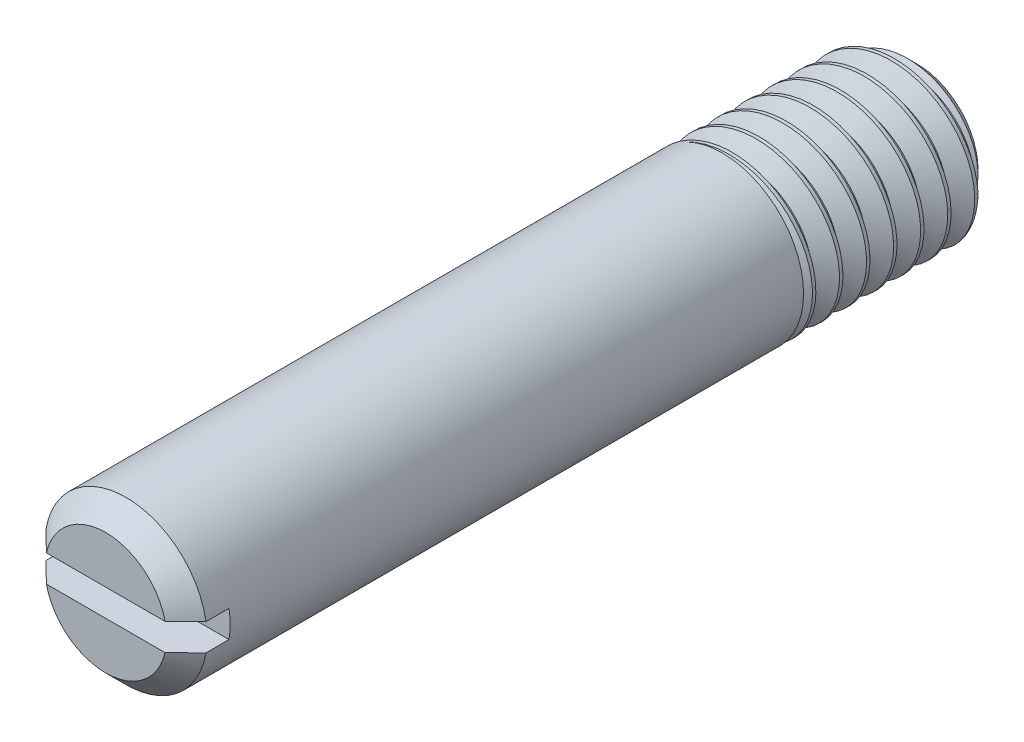
SolidWorks part; units mm, degrees
ref_plane "Front Plane" through (0, 0, 0) normal (0, 0, 1) x (1, 0, 0)
ref_plane "Top Plane" through (0, 0, 0) normal (0, 1, 0) x (1, 0, 0)
ref_plane "Right Plane" through (0, 0, 0) normal (1, 0, 0) x (0, 0, -1)
sketch "Sketch1" plane through (0, 0, 0) normal (1, 0, 0) x (0, 0, -1)
  line L0 (-22.8, 0) -> (7.2, 0) construction
  line L1 (7.2, 3) -> (7.2, -3) construction
  line L2 (-22.8, 0.5) -> (-22.8, -0.5) construction
  line L3 (-22.8, -0.5) -> (-21.2, -0.5) construction
  line L4 (7.2, 3) -> (6.2, 3) construction
  line L5 (6.2, 3) -> (0, 3) construction
  line L6 (0, 3) -> (-22.8, 3) construction
  point P5 (7.2, 0)
  point P9 (0, 0)
  dimension "Oall Length" = 30
  dimension "Thread Diameter" = 6
  dimension "Thread Length" = 7.2
  dimension "Slot Width n" = 1
  dimension "Slot Depth t" = 1.6
  dimension "Pitch" = 1
sketch "Sketch2" plane through (0, 0, 0) normal (1, 0, 0) x (0, 0, -1)
  line L0 (7.2, 0) -> (7.2, 3)
  line L1 (7.2, 3) -> (-22.8, 3)
  line L2 (-22.8, 3) -> (-22.8, 0)
  line L3 (-22.8, 0) -> (7.2, 0)
revolve "Revolve1" add sketch "Sketch2" angle 360 about L0
fillet "Chamfer2" radius 0.75 2 edges at (3, 0, 22.8) (3, 0, -7.2) profile chamfer
sketch "Sketch3" plane through (0, 0, 0) normal (1, 0, 0) x (0, 0, -1)
  line L0 (-21.2, -0.5) -> (-22.8, -0.5)
  line L1 (-22.8, -0.5) -> (-22.8, 0.5)
  line L2 (-22.8, 0.5) -> (-21.2, 0.5)
  line L3 (-21.2, 0.5) -> (-21.2, -0.5)
extrude "Cut-Extrude1" cut sketch "Sketch3" against normal through all both and the other way through all
sketch "Sketch4" plane through (0, 0, -7.2) normal (0, 0, -1) x (-1, 0, 0)
  circle A0 centre (0, 0) radius 3
curve "Helix/Spiral1" pitch 1 height 8.2 radius 3 centre (0, 0, -7.2) axis (0, 0, 1) start towards (0, 1, 0) parameters "pitch"=1
sketch "Sketch5" plane through (0, 0, 0) normal (1, 0, 0) x (0, 0, -1)
  line L0 (7.2, 3) -> (8.075, 3) construction
  line L1 (8.075, 3) -> (7.6375, 2.2422) construction
  line L2 (7.6375, 2.2422) -> (7.2, 3) construction
  line L3 (7.575, 2.3505) -> (7.7, 2.3505) construction
  line L4 (7.6375, 2.3505) -> (7.6375, 3) construction
  line L5 (7.3875, 2.6752) -> (7.8875, 2.6752) construction
  line L6 (7.2, 3) -> (8.075, 3)
  line L7 (8.075, 3) -> (7.7, 2.3505)
  line L8 (7.7, 2.3505) -> (7.575, 2.3505)
  line L9 (7.575, 2.3505) -> (7.2, 3)
  point P7 (7.6375, 2.6752)
  dimension "D1" = 0.125
  dimension "D2" = 0.5
sweep "Cut-Sweep1" cut profiles "Sketch5" path "Helix/Spiral1" align with end faces yes
sketch "Sketch6" plane through (0, 0, 0) normal (0, 0, 1) x (1, 0, 0)
  circle A1 centre (0, 0) radius 3
  circle A2 centre (0, 0) radius 3
  dimension "D1" = 0
extrude "Boss-Extrude2" add sketch "Sketch6" along normal blind 1
ref_axis "Center Axis 1" through (0, 0, -6.45) along (0, 0, 1)
ref_plane "Contact Plane 1" through (0, 0, 0) normal (0, 0, 1) x (1, 0, 0)
equation "\"3..6250in\"=4.625"
equation "\"Slot Width n@Sketch1\"=\"Pitch@Sketch1\""
equation "\"Slot Depth t@Sketch1\"=\"Pitch@Sketch1\"*1.6"
equation "\"D1@Chamfer2\"=\"Pitch@Sketch1\"*.75"
equation "\"D1@Sketch5\"=\"Pitch@Sketch1\"*.125"
equation "\"D2@Sketch5\"=\"Pitch@Sketch1\"*.5"
equation "\"D3@Helix/Spiral1\"=\"Thread Length@Sketch1\"+(\"Pitch@Sketch1\")"
equation "\"D1@Boss-Extrude2\"=\"Pitch@Sketch1\""
